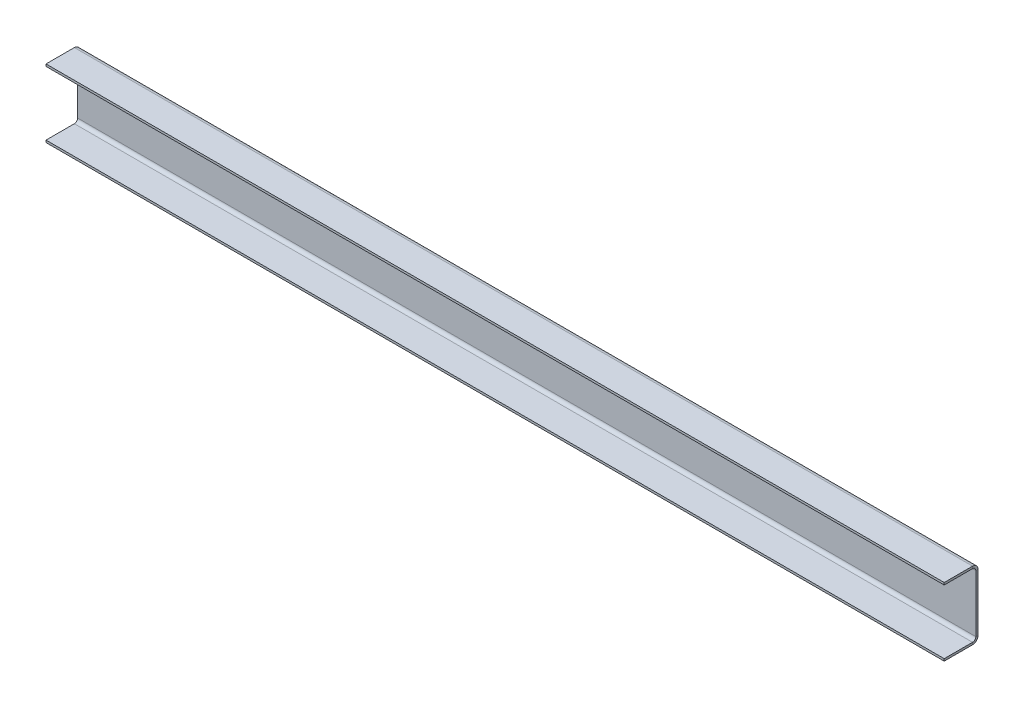
SolidWorks part; units mm, degrees
note: The reader was unsure of these and kept them because the rebuilt part matched: flange length of "Edge-Flange1", "Edge-Flange2".
material "ASTM A36 Steel"
ref_plane "Front Plane" through (0, 0, 0) normal (0, 0, 1) x (1, 0, 0)
ref_plane "Top Plane" through (0, 0, 0) normal (0, 1, 0) x (1, 0, 0)
ref_plane "Right Plane" through (0, 0, 0) normal (1, 0, 0) x (0, 0, -1)
sketch "Sketch1" plane through (0, 0, 0) normal (0, 0, 1) x (1, 0, 0)
  line L1 (483.1277, 106.8867) -> (-1164.8723, 106.8867)
  line L2 (483.1277, 106.8867) -> (483.1277, -18.1133)
  line L3 (483.1277, -18.1133) -> (-1164.8723, -18.1133)
  line L4 (-1164.8723, 106.8867) -> (-1164.8723, -18.1133)
  dimension "D1" = 1648
  dimension "D2" = 125
base flange "Base-Flange1" sketch "Sketch1" thickness 4 reverse thickness direction no parameters "D1"=2.5
edge flange "Edge-Flange1" sketch "Sketch8" flange angle 90 flange length 62 flange position material inside bend radius 6 thickness 4 relief rectangular parameters "D6"=10
sketch "Sketch8" plane through (0, 106.8867, 0) normal (0, -1, 0) x (1, 0, 0)
  line L1 (483.1277, 0) -> (-1164.8723, 0) construction
  line L2 (-1164.8723, 0) -> (-1164.8723, 58)
  line L3 (-1164.8723, 58) -> (483.1277, 58)
  line L4 (483.1277, 58) -> (483.1277, 0)
  line L5 (483.1277, 0) -> (-1164.8723, 0)
bend "EdgeBend1" bend radius 6 bend angle 90 parameters "D5"=1
edge flange "Edge-Flange2" sketch "Sketch11" flange angle 90 flange length 62 flange position material inside bend radius 6 thickness 4 relief rectangular parameters "D6"=10
sketch "Sketch11" plane through (0, -18.1133, 0) normal (0, 1, 0) x (-1, 0, 0)
  line L1 (1164.8723, 0) -> (-483.1277, 0) construction
  line L2 (-483.1277, 0) -> (-483.1277, 58)
  line L3 (-483.1277, 58) -> (1164.8723, 58)
  line L4 (1164.8723, 58) -> (1164.8723, 0)
  line L5 (1164.8723, 0) -> (-483.1277, 0)
bend "EdgeBend2" bend radius 6 bend angle 90 parameters "D5"=2
sketch "Bend-Lines1" [suppressed] plane through (0, 0, 0) normal (0, 1, 0) x (1, 0, 0)
sketch "Bounding-Box1" [suppressed] plane through (0, 0, 0) normal (0, 1, 0) x (1, 0, 0)
sheet metal parameters "Sheet-Metal1" thickness 4 parameters "D1"=2.5
flat pattern "Flat-Pattern1" [suppressed]
sketch "Bend-Lines2" plane through (0, 0, 0) normal (0, 1, 0) x (1, 0, 0)
sketch3d "Bounding-Box2" [suppressed]
  line L0 (708.8723, -18.1133, 0) -> (-483.1277, -18.1133, 0) construction
  line L1 (708.8723, 106.8867, 0) -> (-483.1277, 106.8867, 0) construction
  line L2 (708.8723, -18.1133, 0) -> (708.8723, 106.8867, 0) construction
  line L3 (-483.1277, -18.1133, 0) -> (-483.1277, 106.8867, 0) construction
sheet metal parameters "Sheet-Metal2" thickness 4 parameters "D1"=2.5
flat pattern "Flat-Pattern1"
sketch "Bend-Lines2" plane through (0, 0, 0) normal (0, 0, 1) x (1, 0, 0)
  line L0 (483.1277, 103.1698) -> (-708.8723, 103.1698) construction
  line L1 (483.1277, 103.1698) -> (-708.8723, 103.1698) construction
sketch3d "Bounding-Box2" [suppressed]
  line L0 (-708.8723, -18.1133, 0) -> (483.1277, -18.1133, 0) construction
  line L1 (-708.8723, 161.453, 0) -> (483.1277, 161.453, 0) construction
  line L2 (-708.8723, -18.1133, 0) -> (-708.8723, 161.453, 0) construction
  line L3 (483.1277, -18.1133, 0) -> (483.1277, 161.453, 0) construction
bend of the flat pattern "Flatten-<EdgeBend1>1"
sheet metal parameters "Sheet-Metal3" thickness 4 parameters "D1"=2.5
flat pattern "Flat-Pattern1"
sketch "Bend-Lines2" plane through (0, 0, 0) normal (0, 0, 1) x (1, 0, 0)
  line L0 (483.1277, 103.1698) -> (-1164.8723, 103.1698) construction
  line L1 (483.1277, 103.1698) -> (-1164.8723, 103.1698) construction
  line L2 (-1164.8723, -14.3965) -> (483.1277, -14.3965) construction
  line L3 (-1164.8723, -14.3965) -> (483.1277, -14.3965) construction
sketch3d "Bounding-Box2" [suppressed]
  line L0 (-1164.8723, -72.6797, 0) -> (483.1277, -72.6797, 0) construction
  line L1 (-1164.8723, 161.453, 0) -> (483.1277, 161.453, 0) construction
  line L2 (-1164.8723, -72.6797, 0) -> (-1164.8723, 161.453, 0) construction
  line L3 (483.1277, -72.6797, 0) -> (483.1277, 161.453, 0) construction
bend of the flat pattern "Flatten-<EdgeBend1>1"
bend of the flat pattern "Flatten-<EdgeBend2>1"
